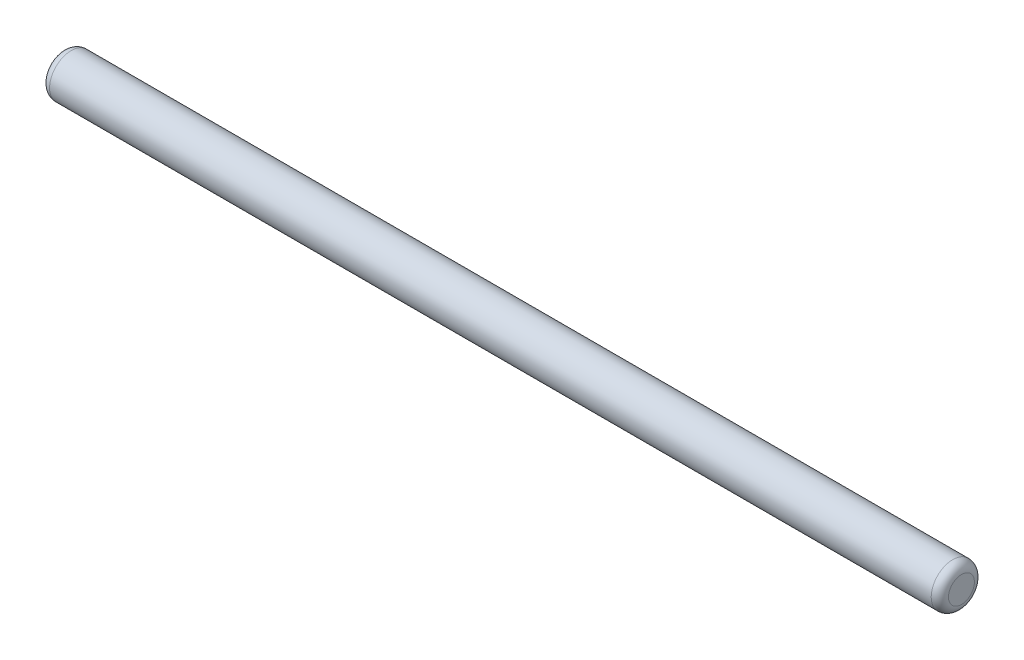
SolidWorks part; units mm, degrees
ref_plane "Front Plane" through (0, 0, 0) normal (1, 0, 0) x (0, 1, 0)
ref_plane "Top Plane" through (0, 0, 0) normal (0, 0, 1) x (0, 1, 0)
ref_plane "Right Plane" through (0, 0, 0) normal (0, 1, 0) x (-1, 0, 0)
sketch "Sketch1" plane through (0, 0, 0) normal (1, 0, 0) x (0, 1, 0)
  circle A0 centre (0, 0) radius 2.5
  dimension "D1" = 5
extrude "Boss-Extrude1" add sketch "Sketch1" along normal blind 104
fillet "Fillet1" radius 1 2 edges at (0, 0, -2.5) (104, 0, -2.5)
